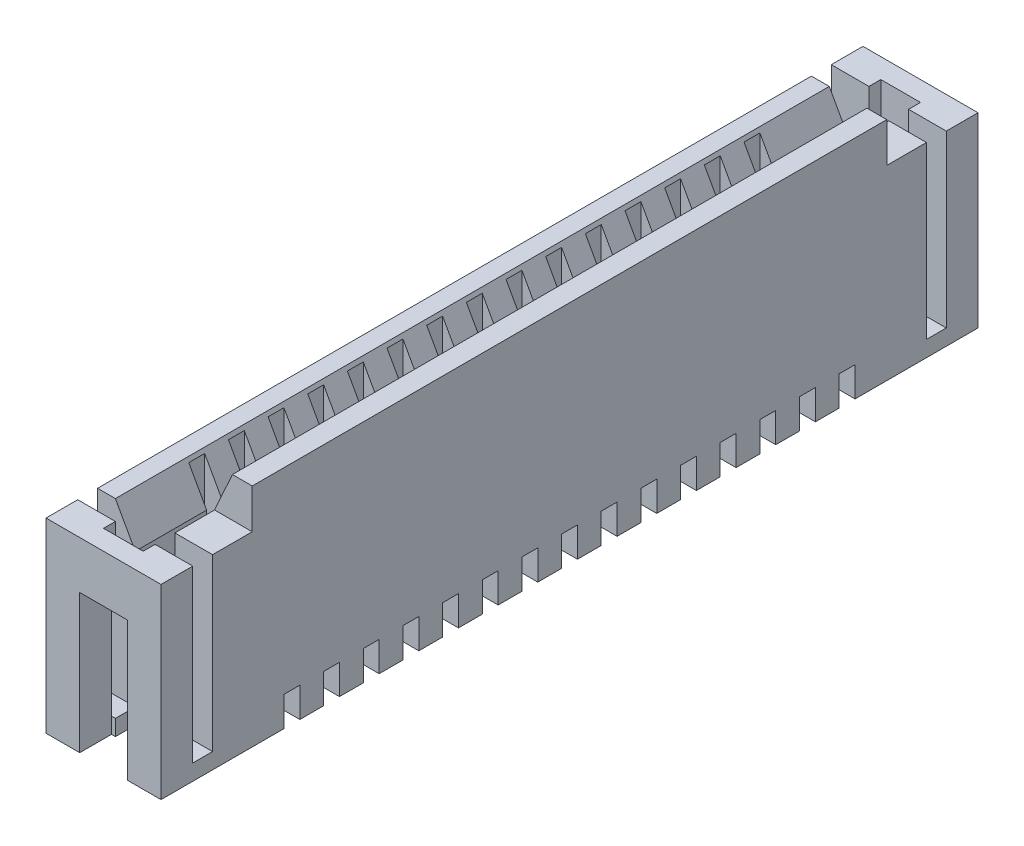
SolidWorks part; units mm, degrees
ref_plane "Plano frontal" through (0, 0, 0) normal (0, 0, 1) x (1, 0, 0)
ref_plane "Plano superior" through (0, 0, 0) normal (0, 1, 0) x (1, 0, 0)
ref_plane "Plano direito" through (0, 0, 0) normal (1, 0, 0) x (0, 0, -1)
sketch "Esboço1" plane through (0, 0, 0) normal (0, 1, 0) x (1, 0, 0)
  line L1 (-1.45, -10.3) -> (1.45, -10.3)
  line L2 (-1.45, -10.3) -> (-1.45, 10.3)
  line L3 (-1.45, 10.3) -> (1.45, 10.3)
  line L4 (1.45, -10.3) -> (1.45, 10.3)
  line L5 (-1.45, -10.3) -> (1.45, 10.3) construction
  line L6 (-1.45, 10.3) -> (1.45, -10.3) construction
  point P0 (0, 0)
  dimension "D1" = 20.6
  dimension "D2" = 2.9
extrude "Ressalto-extrusão1" add sketch "Esboço1" along normal blind 4.7
sketch "Esboço2" plane through (0, 4.7, 0) normal (0, 1, 0) x (1, 0, 0)
  line L1 (-0.5, -9.8) -> (0.5, -9.8)
  line L2 (-0.5, -9.8) -> (-0.5, 9.8)
  line L3 (-0.5, 9.8) -> (0.5, 9.8)
  line L4 (0.5, -9.8) -> (0.5, 9.8)
  line L5 (-0.5, -9.8) -> (0.5, 9.8) construction
  line L6 (-0.5, 9.8) -> (0.5, -9.8) construction
  point P0 (0, 0)
  dimension "D1" = 19.6
  dimension "D2" = 1
extrude "Corte-extrusão1" cut sketch "Esboço2" against normal blind 4.3
sketch "Esboço3" plane through (0, 4.7, 0) normal (0, 1, 0) x (1, 0, 0)
  line L1 (-3.2854, 9.5) -> (3.6069, 9.5)
  line L2 (-3.2854, 9.5) -> (-3.2854, 9)
  line L3 (-3.2854, 9) -> (3.6069, 9)
  line L4 (3.6069, 9.5) -> (3.6069, 9)
  line L5 (-3.2854, -9) -> (4.0468, -9)
  line L6 (-3.2854, -9) -> (-3.2854, -9.5)
  line L7 (-3.2854, -9.5) -> (4.0468, -9.5)
  line L8 (4.0468, -9) -> (4.0468, -9.5)
  dimension "D1" = 9
  dimension "D2" = 9
  dimension "D3" = 0.5
  dimension "D4" = 0.5
extrude "Corte-extrusão2" cut sketch "Esboço3" against normal blind 4.3
chamfer "Chanfro2" distance 0.5 angle 61 1 edges at (-0.5, 4.7, 0) first distance on face at (-0.975, 4.7, 0)
sketch "Esboço4" plane through (0, 0, 0) normal (0, 0, 1) x (1, 0, 0)
  line L0 (1.45, 4.7) -> (1.45, 5.7)
  line L1 (1.45, 5.7) -> (0.95, 5.7)
  line L2 (0.95, 5.7) -> (0.5, 4.7)
  line L3 (-1.45, 4.7) -> (1.45, 4.7) construction
  line L4 (0.5, 4.7) -> (1.45, 4.7)
  dimension "D1" = 0.95
  dimension "D2" = 1
  dimension "D3" = 0.5
extrude "Ressalto-extrusão2" add sketch "Esboço4" along normal mid plane 16
sketch "Esboço5" plane through (0, 0.4, 0) normal (0, 1, 0) x (1, 0, 0)
  line L0 (0.5, -9) -> (0.5, 9) construction
  line L1 (-0.5, 9.8) -> (0.5, 9.8)
  line L2 (-0.5, 9.8) -> (-0.5, 8.7)
  line L3 (-0.5, 8.7) -> (0.5, 8.7)
  line L4 (0.5, 9.8) -> (0.5, 8.7)
  line L5 (-0.5, 9) -> (-0.5, -9) construction
  line L6 (0.5, -9.8) -> (-0.5, -9.8)
  line L7 (0.5, -9.8) -> (0.5, -8.7)
  line L8 (0.5, -8.7) -> (-0.5, -8.7)
  line L9 (-0.5, -9.8) -> (-0.5, -8.7)
  dimension "D1" = 1.1
  dimension "D2" = 1.1
extrude "Corte-extrusão3" cut sketch "Esboço5" against normal blind 2
sketch "Esboço6" plane through (0, 0.4, 0) normal (0, 1, 0) x (1, 0, 0)
  line L0 (0.5, -8.7) -> (0.5, 8.7) construction
  line L1 (-0.5, 8.7) -> (0.5, 8.7)
  line L2 (-0.5, 8.7) -> (-0.5, 8.3)
  line L3 (-0.5, 8.3) -> (0.5, 8.3)
  line L4 (0.5, 8.7) -> (0.5, 8.3)
  line L5 (-0.5, 8.7) -> (-0.5, -8.7) construction
  line L6 (0.5, -8.7) -> (-0.5, -8.7)
  line L7 (0.5, -8.7) -> (0.5, -8.3)
  line L8 (0.5, -8.3) -> (-0.5, -8.3)
  line L9 (-0.5, -8.7) -> (-0.5, -8.3)
  dimension "D1" = 0.4
  dimension "D2" = 0.4
extrude "Ressalto-extrusão3" add sketch "Esboço6" along normal blind 2
sketch "Esboço7" plane through (0, 4.7, 0) normal (0, 1, 0) x (1, 0, 0)
  line L0 (-1.45, 9) -> (-1.45, -9) construction
  line L1 (-0.95, 0.2) -> (-0.25, 0.2)
  line L2 (-0.95, 0.2) -> (-0.95, -0.2)
  line L3 (-0.95, -0.2) -> (-0.25, -0.2)
  line L4 (-0.25, 0.2) -> (-0.25, -0.2)
  line L5 (1.45, -8) -> (1.45, 8) construction
  line L6 (0.25, 0.2) -> (0.95, 0.2)
  line L7 (0.25, 0.2) -> (0.25, -0.2)
  line L8 (0.25, -0.2) -> (0.95, -0.2)
  line L9 (0.95, 0.2) -> (0.95, -0.2)
  dimension "D1" = 0.7
  dimension "D2" = 0.4
  dimension "D3" = 0.2
  dimension "D4" = 0.5
  dimension "D5" = 0.5
  dimension "D6" = 0.7
extrude "Corte-extrusão4" cut sketch "Esboço7" against normal blind 4.3 and the other way blind 2
sketch "Esboço8" plane through (0, 0, 0) normal (1, 0, 0) x (0, 0, -1)
  line L1 (0.2, -0.25) -> (-0.2, -0.25)
  line L2 (0.2, -0.25) -> (0.2, 0.75)
  line L3 (0.2, 0.75) -> (-0.2, 0.75)
  line L4 (-0.2, -0.25) -> (-0.2, 0.75)
  line L5 (0.2, -0.25) -> (-0.2, 0.75) construction
  line L6 (0.2, 0.75) -> (-0.2, -0.25) construction
  line L7 (10.3, 0) -> (-10.3, 0) construction
  point P0 (0, 0.25)
  dimension "D1" = 0.4
  dimension "D2" = 0
  dimension "D3" = 1
  dimension "D4" = 0.75
extrude "Corte-extrusão7" cut sketch "Esboço8" against normal mid plane 12.1
pattern_linear "Padrão linear1" count 8 spacing 1 along (0, 0, 1) count 8 spacing 1 along (0, 0, -1) of "Corte-extrusão4", "Corte-extrusão7"
sketch "Esboço9" plane through (0, 0, 10.3) normal (0, 0, 1) x (1, 0, 0)
  line L0 (-1.45, 0) -> (1.45, 0) construction
  line L1 (-0.6, 3.5) -> (0.6, 3.5)
  line L2 (-0.6, 3.5) -> (-0.6, -0.9373)
  line L3 (-0.6, -0.9373) -> (0.6, -0.9373)
  line L4 (0.6, 3.5) -> (0.6, -0.9373)
  dimension "D1" = 3.5
  dimension "D2" = 1.2
  dimension "D3" = 0.6
extrude "Corte-extrusão6" cut sketch "Esboço9" against normal blind 0.8
mirror "Espelhar1" about plane through (0, 0, 0) normal (0, 0, 1) of "Corte-extrusão6"
